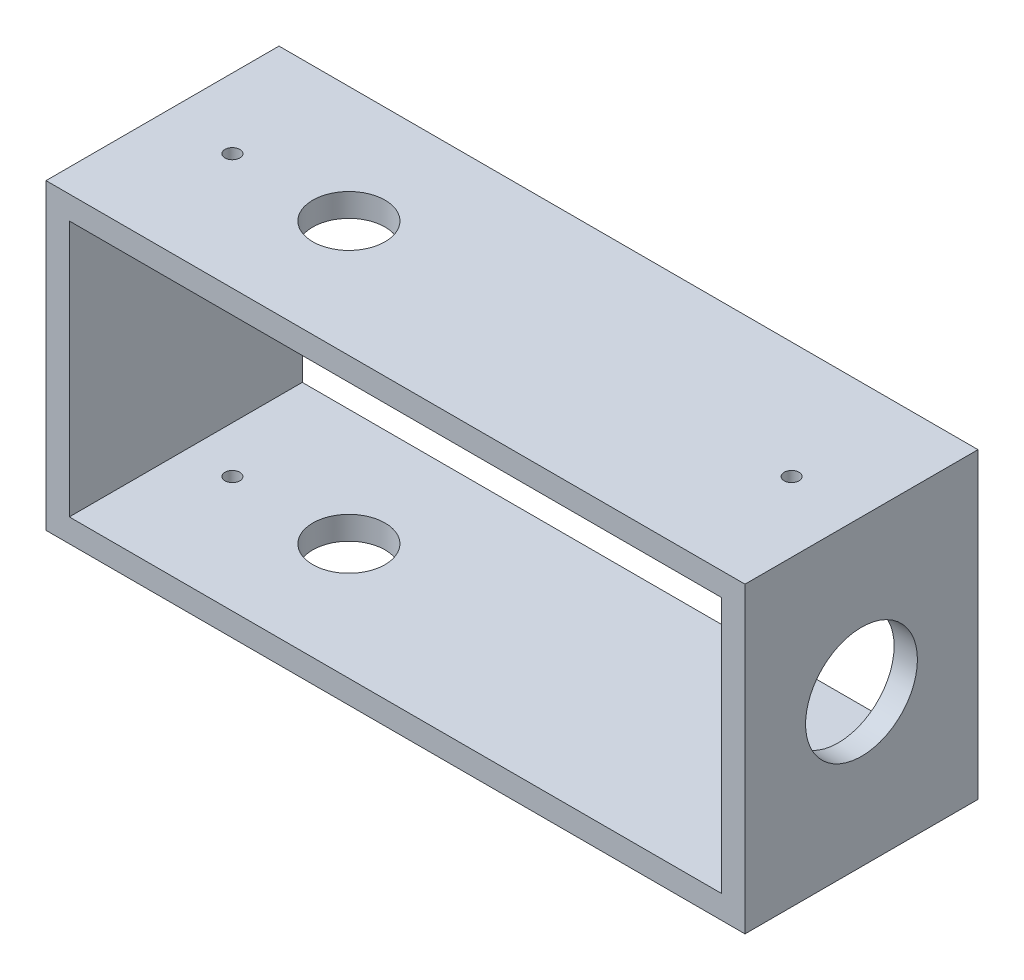
SolidWorks part; units mm, degrees
ref_plane "Front Plane" through (0, 0, 0) normal (1, 0, 0) x (0, 1, 0)
ref_plane "Top Plane" through (0, 0, 0) normal (0, 0, 1) x (0, 1, 0)
ref_plane "Right Plane" through (0, 0, 0) normal (0, 1, 0) x (-1, 0, 0)
sketch "Sketch1" plane through (0, 0, 0) normal (0, 0, 1) x (0, 1, 0)
  line L5 (-32.5, -75) -> (32.5, -75)
  line L6 (-32.5, -75) -> (-32.5, 75)
  line L7 (-32.5, 75) -> (32.5, 75)
  line L8 (32.5, -75) -> (32.5, 75)
  line L9 (-32.5, -75) -> (32.5, 75) construction
  line L10 (-32.5, 75) -> (32.5, -75) construction
  line L11 (-27.5, -70) -> (27.5, -70)
  line L12 (-27.5, -70) -> (-27.5, 70)
  line L13 (-27.5, 70) -> (27.5, 70)
  line L14 (27.5, -70) -> (27.5, 70)
  line L15 (-27.5, -70) -> (27.5, 70) construction
  line L16 (-27.5, 70) -> (27.5, -70) construction
  point P0 (0, 0)
  point P6 (0, 0)
  dimension "D1" = 65
  dimension "D2" = 150
  dimension "D3" = 5
  dimension "D4" = 5
extrude "Boss-Extrude1" add sketch "Sketch1" along normal blind 50
sketch "Sketch2" plane through (0, -32.5, 0) normal (0, -1, 0) x (1, 0, 0)
  line L0 (-75, 25) -> (75, 25) construction
  line L1 (-75, 50) -> (-75, 0) construction
  line L2 (75, 50) -> (75, 0) construction
  circle A0 centre (-60, 25) radius 1.6
  circle A1 centre (60, 25) radius 1.6
  dimension "D1" = 15
  dimension "D2" = 15
  dimension "D3" = 3.2
extrude "Cut-Extrude1" cut sketch "Sketch2" against normal through all
sketch "Sketch3" plane through (0, -32.5, 0) normal (0, -1, 0) x (1, 0, 0)
  line L0 (-75, 25) -> (75, 25) construction
  line L1 (-75, 50) -> (-75, 0) construction
  line L2 (75, 50) -> (75, 0) construction
  circle A0 centre (-35, 25) radius 7.75
  dimension "D1" = 15.5
  dimension "D2" = 40
extrude "Cut-Extrude2" cut sketch "Sketch3" against normal through all
sketch "Sketch4" plane through (75, 0, 0) normal (1, 0, 0) x (0, 1, 0)
  line L0 (0, 50) -> (0, 0) construction
  line L1 (-32.5, 50) -> (32.5, 50) construction
  line L2 (-32.5, 0) -> (32.5, 0) construction
  circle A1 centre (0, 25) radius 12
  dimension "D1" = 24
extrude "Cut-Extrude3" cut sketch "Sketch4" against normal up to surface (5 mm away) up to face at (70, 0, 25)
